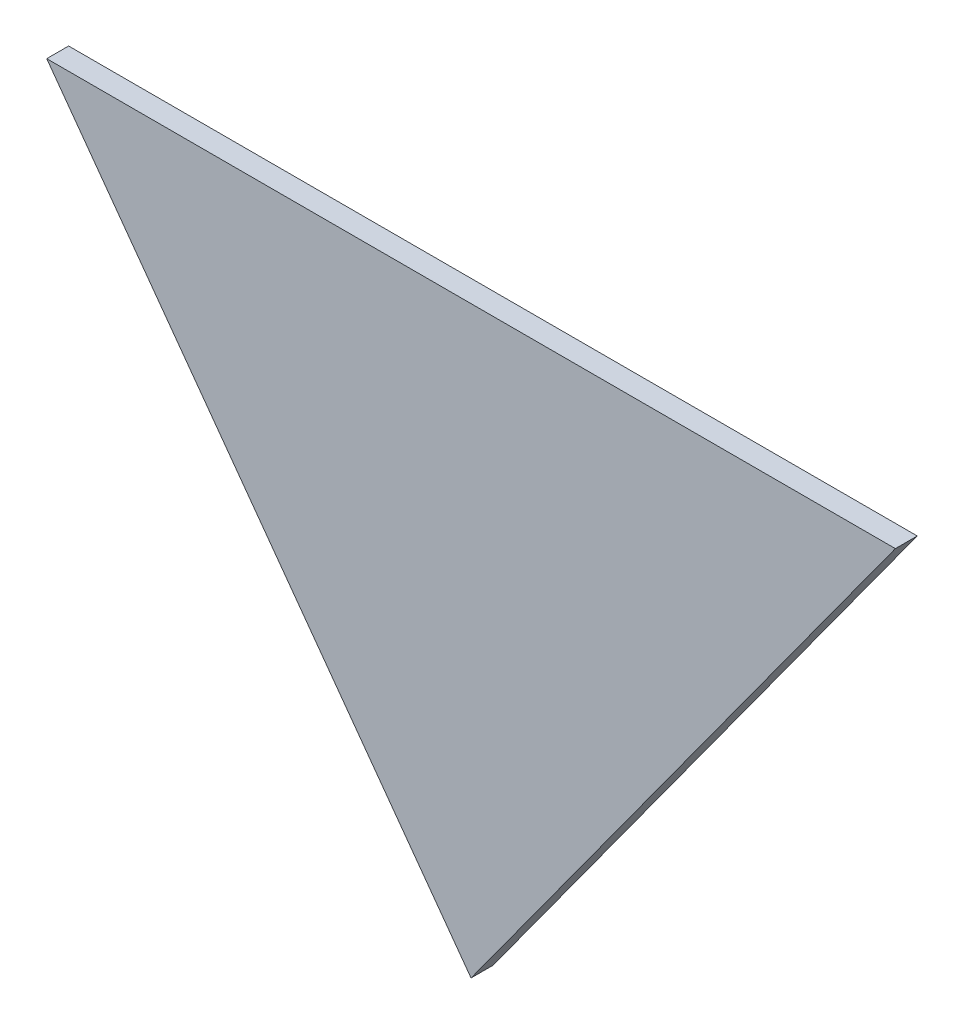
SolidWorks part; units mm, degrees
ref_plane "Front Plane" through (0, 0, 0) normal (0, 0, 1) x (1, 0, 0)
ref_plane "Top Plane" through (0, 0, 0) normal (0, 1, 0) x (1, 0, 0)
ref_plane "Right Plane" through (0, 0, 0) normal (1, 0, 0) x (0, 0, -1)
sketch "Sketch3" plane through (0, 0, 0) normal (0, 0, 1) x (1, 0, 0)
  line L0 (0, 0) -> (54.4907, 75)
  line L1 (54.4907, 75) -> (-54.4907, 75)
  line L2 (-54.4907, 75) -> (0, 0)
  point P3 (0, 0)
  point P5 (0, 75)
  dimension "D1" = 72
  dimension "D2" = 75
extrude "Boss-Extrude1" add sketch "Sketch3" along normal blind 3
ref_plane "Offset_R" through (0, 75, 0) normal (0, 1, 0) x (1, 0, 0)
sketch "Sketch4" plane through (0, 0, 0) normal (0, 0, -1) x (-1, 0, 0)
  line L0 (-54.4907, 75) -> (-58.1234, 80)
  line L1 (-58.1234, 80) -> (58.1234, 80)
  line L2 (58.1234, 80) -> (54.4907, 75)
  line L3 (54.4907, 75) -> (-54.4907, 75)
  line L4 (0, 0) -> (-54.4907, 75) construction
  line L5 (54.4907, 75) -> (0, 0) construction
  dimension "D1" = 5
extrude "Boss-Extrude2" add sketch "Sketch4" against normal up to surface (3 mm away) up to face at (0, 50, 3)
